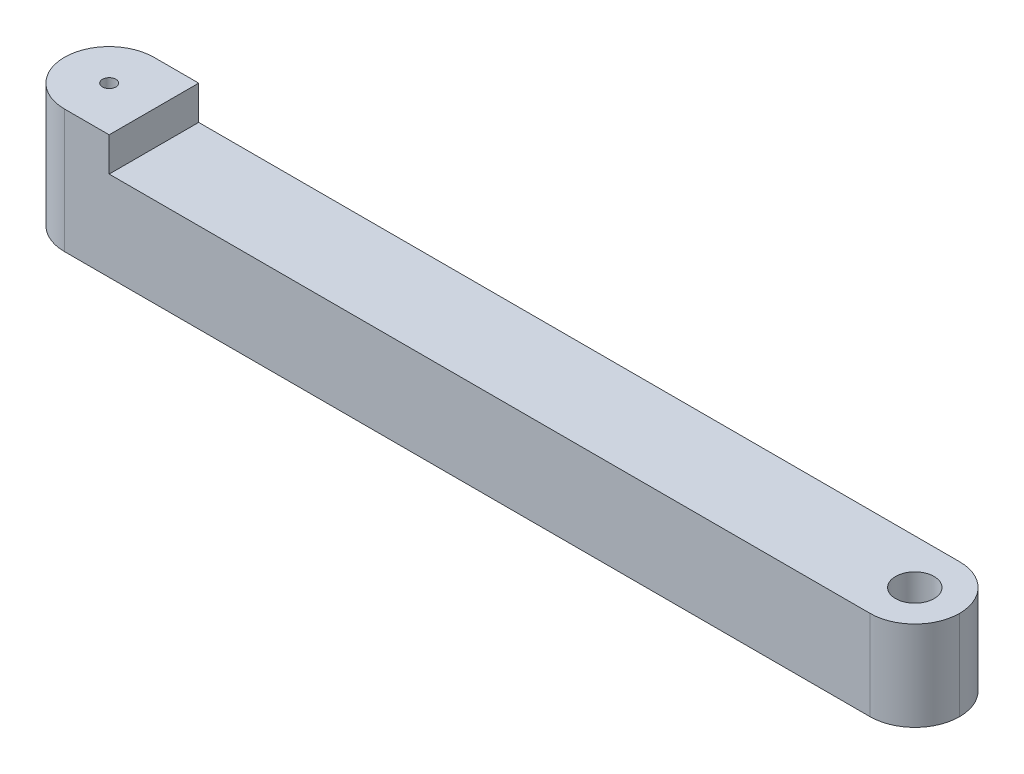
SolidWorks part; units mm, degrees
ref_plane "정면" through (0, 0, 0) normal (0, 0, 1) x (1, 0, 0)
ref_plane "윗면" through (0, 0, 0) normal (0, 1, 0) x (1, 0, 0)
ref_plane "우측면" through (0, 0, 0) normal (1, 0, 0) x (0, 0, -1)
sketch "스케치1" plane through (0, 0, 0) normal (0, 0, 1) x (1, 0, 0)
  line L1 (-50, -5) -> (50, -5)
  line L2 (-50, -5) -> (-50, 5)
  line L3 (-50, 5) -> (50, 5)
  line L4 (50, -5) -> (50, 5)
  line L5 (-50, -5) -> (50, 5) construction
  line L6 (-50, 5) -> (50, -5) construction
  point P0 (0, 0)
  dimension "D1" = 100
  dimension "D2" = 10
extrude "보스-돌출1" add sketch "스케치1" along normal blind 10
sketch "스케치4" plane through (0, 5, 0) normal (0, 1, 0) x (1, 0, 0)
  line L0 (50, 0) -> (-50, 0) construction
  line L1 (-40, 0) -> (-50, 0)
  line L2 (-40, 0) -> (-40, -10)
  line L3 (-40, -10) -> (-50, -10)
  line L4 (-50, 0) -> (-50, -10)
  dimension "D1" = 10
extrude "보스-돌출2" add sketch "스케치4" along normal blind 3.8
fillet "필렛1" radius 5 4 edges at (50, 0, 10) (50, 0, 0) (-50, 1.9, 0) (-50, 1.9, 10)
sketch "스케치2" plane through (0, 8.8, 0) normal (0, 1, 0) x (1, 0, 0)
  circle A0 centre (-45, -5) radius 0.75
  circle A1 centre (45, -5) radius 2.15
  dimension "D1" = 1.5
  dimension "D2" = 4.3
extrude "컷-돌출1" cut sketch "스케치2" against normal through all
